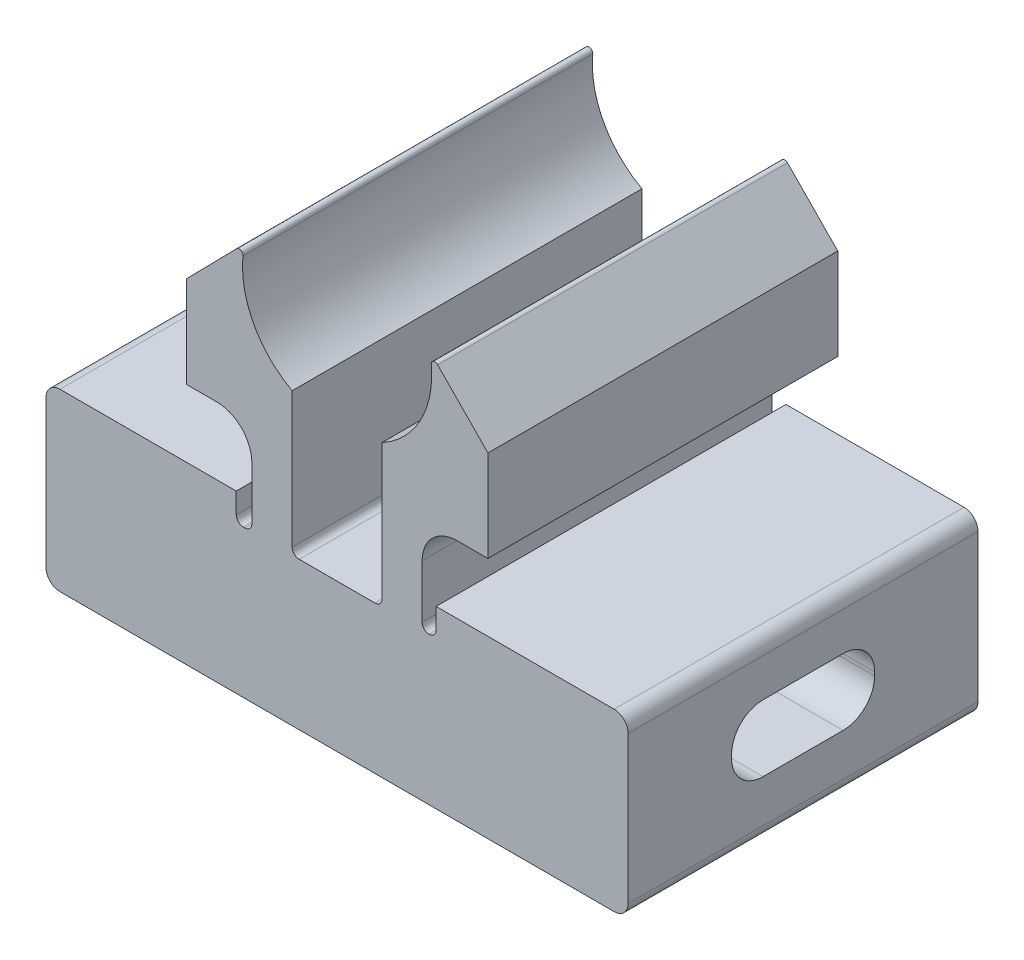
SolidWorks part; units mm, degrees
ref_plane "Front Plane" through (0, 0, 0) normal (0, 0, 1) x (1, 0, 0)
ref_plane "Top Plane" through (0, 0, 0) normal (0, 1, 0) x (1, 0, 0)
ref_plane "Right Plane" through (0, 0, 0) normal (1, 0, 0) x (0, 0, -1)
sketch "Sketch2" plane through (0, 0, 0) normal (0, 0, 1) x (1, 0, 0)
  line L0 (-5.4715, -10.4902) -> (-4.3637, -10.4902)
  line L1 (-3.0937, -11.7602) -> (-3.0937, -12.9378)
  line L2 (-3.0937, -12.9378) -> (-10.5664, -12.9378)
  line L3 (-10.5664, -12.9378) -> (-10.5664, -19.302)
  line L4 (-10.5664, -19.302) -> (10.5664, -19.302)
  line L5 (10.5664, -19.302) -> (10.5664, -12.9378)
  line L6 (10.5664, -12.9378) -> (3.0867, -12.9378)
  line L7 (3.0867, -12.9378) -> (3.0867, -11.7602)
  line L8 (4.3567, -10.4902) -> (5.476, -10.4902)
  line L11 (-3.6504, -5.3147) -> (-5.4715, -7.1736)
  line L12 (3.6502, -5.3139) -> (5.476, -7.1735)
  line L13 (5.476, -10.4902) -> (5.476, -7.1735)
  line L14 (-5.4715, -10.4902) -> (-5.4715, -7.1736)
  arc A0 (3.0867, -11.7602) -> (4.3567, -10.4902) centre (4.3567, -11.7602) cw
  arc A1 (-4.3637, -10.4902) -> (-3.0937, -11.7602) centre (-4.3637, -11.7602) cw
  arc A2 (-3.4187, -5.4224) -> (3.4186, -5.4217) centre (0, -5.7477) ccw
  arc A3 (-1.6181, -4.4958) -> (-3.8632, -5.4257) centre (-1.6181, -7.6708) ccw construction
  arc A4 (3.8632, -5.4257) -> (1.6181, -4.4958) centre (1.6181, -7.6708) ccw construction
  arc A5 (-3.4187, -5.4224) -> (-3.6504, -5.3147) centre (-3.5536, -5.4095) ccw
  arc A6 (3.4186, -5.4217) -> (3.6502, -5.3139) centre (3.5535, -5.4088) cw
  point P0 (-5.4715, -7.1736)
  point P27 (-3.3546, -5.0127)
  point P30 (3.3546, -5.0127)
  dimension "D1" = 1.27
  dimension "D2" = 0.1355
  dimension "D3" = 0.1355
extrude "Boss-Extrude9" add sketch "Sketch2" along normal mid plane 12.7
sketch "Sketch4" plane through (0, 0, 6.35) normal (0, 0, 1) x (1, 0, 0)
  line L1 (-1.6308, -13.9408) -> (1.6308, -13.9408)
  line L2 (-1.6308, -13.9408) -> (-1.6308, -9.9754)
  line L3 (-1.6308, -9.9754) -> (1.6308, -9.9754)
  line L4 (1.6308, -13.9408) -> (1.6308, -9.9754)
  line L5 (-1.6308, -13.9408) -> (1.6308, -9.9754) construction
  line L6 (-1.6308, -9.9754) -> (1.6308, -13.9408) construction
  point P0 (0, -11.9581)
extrude "Cut-Extrude2" cut sketch "Sketch4" against normal through all
sketch "Sketch5" plane through (0, 0, 6.35) normal (0, 0, 1) x (1, 0, 0)
  line L0 (-1.6308, -9.9754) -> (0, -9.9754)
  line L1 (-1.6308, -9.9754) -> (-1.6308, -8.7082)
  line L2 (0, -9.9754) -> (0, -8.7082)
  line L3 (-1.6308, -8.7082) -> (0, -8.7082)
  line L4 (1.6308, -9.9754) -> (-1.6308, -9.9754) construction
extrude "Cut-Extrude6" cut sketch "Sketch5" against normal through all
sketch "Sketch6" plane through (0, 0, -6.35) normal (0, 0, -1) x (-1, 0, 0)
  line L0 (-1.6308, -9.9754) -> (0, -9.9754)
  line L1 (-1.6308, -9.9754) -> (-1.6308, -8.7279)
  line L2 (0, -9.9754) -> (0, -8.7279)
  line L3 (-1.6308, -8.7279) -> (0, -8.7279)
extrude "Cut-Extrude7" cut sketch "Sketch6" against normal through all
sketch "Sketch8" plane through (0, 0, 0) normal (0, 0, 1) x (1, 0, 0)
  line L0 (-3.0937, -12.9378) -> (-3.0937, -13.9408)
  line L1 (-3.0937, -12.9378) -> (-3.6606, -12.9378)
  line L2 (-3.0937, -13.9408) -> (-3.6606, -13.9408)
  line L3 (-3.6606, -12.9378) -> (-3.6606, -13.9408)
extrude "Cut-Extrude9" cut sketch "Sketch8" against normal through all both and the other way through all
sketch "Sketch9" plane through (0, 0, 6.35) normal (0, 0, 1) x (1, 0, 0)
  line L0 (3.0867, -12.9378) -> (3.0867, -13.9408)
  line L1 (3.0867, -12.9378) -> (3.5947, -12.9378)
  line L2 (3.0867, -13.9408) -> (3.5947, -13.9408)
  line L3 (3.5947, -12.9378) -> (3.5947, -13.9408)
extrude "Cut-Extrude10" cut sketch "Sketch9" against normal through all both and the other way through all
fillet "Fillet1" radius 0.254 1 edges at (-3.0937, -13.9408, 0)
fillet "Fillet2" radius 0.254 1 edges at (-3.6606, -13.9408, 0)
fillet "Fillet3" radius 0.254 4 edges at (-1.6308, -13.9408, 0) (1.6308, -13.9408, 0) (3.5947, -13.9408, 0) (3.0867, -13.9408, 0)
fillet "Fillet4" radius 0.508 1 edges at (-10.5664, -12.9378, 0)
fillet "Fillet5" radius 0.508 3 edges at (10.5664, -12.9378, 0) (10.5664, -19.302, 0) (-10.5664, -19.302, 0)
sketch "Sketch11" plane through (-10.5664, 0, 0) normal (-1, 0, 0) x (0, 0, 1)
  line L1 (-2.5952, -14.8365) -> (2.5952, -14.8365)
  line L2 (-2.5952, -14.8365) -> (-2.5952, -17.2517)
  line L3 (-2.5952, -17.2517) -> (2.5952, -17.2517)
  line L4 (2.5952, -14.8365) -> (2.5952, -17.2517)
  line L5 (-2.5952, -14.8365) -> (2.5952, -17.2517) construction
  line L6 (-2.5952, -17.2517) -> (2.5952, -14.8365) construction
  point P0 (0, -16.0441)
extrude "Cut-Extrude11" cut sketch "Sketch11" against normal through all
fillet "Fillet6" radius 1.143 4 edges at (0, -14.8365, -2.5952) (0, -17.2517, -2.5952) (0, -17.2517, 2.5952) (0, -14.8365, 2.5952)
